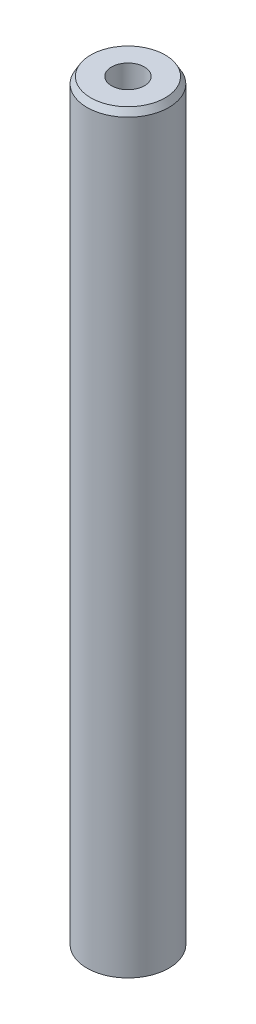
SolidWorks part; units mm, degrees
ref_plane "Front Plane" through (0, 0, 0) normal (0, 0, 1) x (1, 0, 0)
ref_plane "Top Plane" through (0, 0, 0) normal (0, 1, 0) x (1, 0, 0)
ref_plane "Right Plane" through (0, 0, 0) normal (1, 0, 0) x (0, 0, -1)
sketch "Sketch1" plane through (0, 0, 0) normal (0, 1, 0) x (1, 0, 0)
  circle A0 centre (0, 0) radius 32.5
  dimension "SHAFT_OD" = 65
extrude "Boss-Extrude1" add sketch "Sketch1" along normal blind 600
sketch "Sketch2" plane through (0, 0, 0) normal (0, 1, 0) x (1, 0, 0)
  circle A0 centre (0, 0) radius 13.0248
  dimension "BORE_D" = 26.0496
extrude "Cut-Extrude1" cut sketch "Sketch2" along normal through all
chamfer "Chamfer1" distance 5.1385 angle 30 2 edges at (0, 600, 32.5) (0, 0, 32.5) first distance on face at (0, 600, 32.5) first distance on face at (0, 0, 13.0248)
